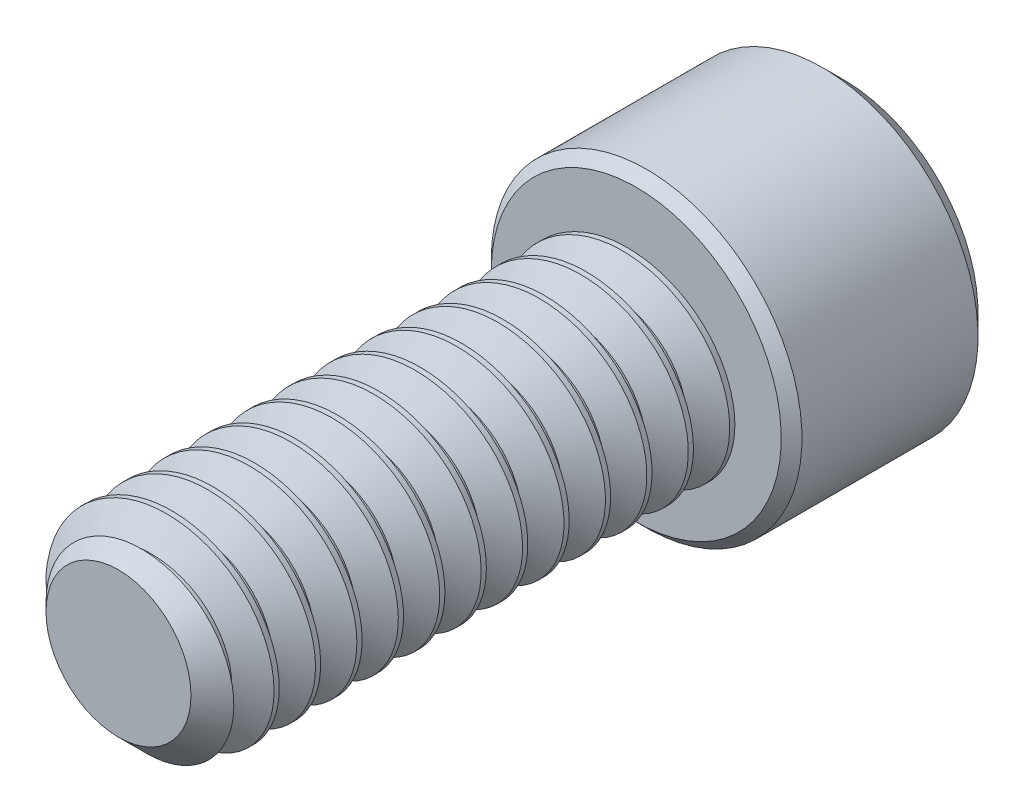
SolidWorks part; units mm, degrees
ref_plane "Front Plane" through (0, 0, 0) normal (0, 0, 1) x (1, 0, 0)
ref_plane "Top Plane" through (0, 0, 0) normal (0, 1, 0) x (1, 0, 0)
ref_plane "Right Plane" through (0, 0, 0) normal (1, 0, 0) x (0, 0, -1)
sketch "Sketch1" plane through (0, 0, 0) normal (0, 0, 1) x (1, 0, 0)
  line L0 (0, 3.175) -> (0, -3.175) construction
  circle A0 centre (0, 0) radius 3.175
  dimension "OD" = 6.35
extrude "Extrude1" add sketch "Sketch1" against normal blind 15.875
sketch "Sketch2" plane through (0, 0, 0) normal (0, 0, 1) x (1, 0, 0)
  circle A0 centre (0, 0) radius 3.175 construction
  circle A1 centre (0, 0) radius 3.175
curve "Helix/Spiral1" pitch 1.27 height 17.145 turns 13.5 parameters "pitch"=1.27
chamfer "Chamfer3" distance 0.9525 angle 45 1 edges at (3.175, 0, 0)
sketch "Sketch3" plane through (0, 0, 0) normal (1, 0, 0) x (0, 0, -1)
  line L0 (-1.1113, 3.175) -> (-0.635, 2.3501)
  line L1 (-0.635, 2.3501) -> (-0.4763, 2.3501)
  line L2 (-0.4763, 2.3501) -> (0, 3.175)
  line L3 (-1.1113, 3.175) -> (0, 3.175)
  line L4 (-0.5556, 3.175) -> (-0.5556, 2.3501) construction
  line L5 (-0.8731, 2.7626) -> (-0.2381, 2.7626) construction
  line L6 (0, 3.175) -> (0, -3.175) construction
  dimension "D1" = 0.1588
  dimension "D2" = 0.635
  dimension "D3" = 60
sweep "Cut-Sweep1" cut profiles "Sketch3" path "Helix/Spiral1"
sketch "Sketch6" plane through (0, 0, -15.875) normal (0, 0, -1) x (-1, 0, 0)
  circle A0 centre (0, 0) radius 4.7625
  dimension "head dia" = 9.525
extrude "Extrude2" add sketch "Sketch6" along normal blind 6.35
sketch "Sketch7" plane through (0, 0, -22.225) normal (0, 0, -1) x (-1, 0, 0)
  line L1 (0, 2.7496) -> (-2.3813, 1.3748)
  line L2 (-2.3813, 1.3748) -> (-2.3813, -1.3748)
  line L3 (-2.3813, -1.3748) -> (0, -2.7496)
  line L4 (0, -2.7496) -> (2.3813, -1.3748)
  line L5 (2.3813, -1.3748) -> (2.3813, 1.3748)
  line L6 (2.3813, 1.3748) -> (0, 2.7496)
  circle A0 centre (0, 0) radius 2.3813 construction
  dimension "hex dia" = 4.7625
extrude "Cut-Extrude1" cut sketch "Sketch7" against normal blind 3.5719
sketch "Sketch8" plane through (0, 0, -22.225) normal (0, 0, -1) x (-1, 0, 0)
  circle A0 centre (0, 0) radius 2.7496
extrude "Cut-Extrude2" cut sketch "Sketch8" against normal blind 0.635 draft 45
chamfer "Chamfer1" distance 0.635 angle 45 1 edges at (-4.7625, 0, -22.225)
chamfer "Chamfer2" distance 0.3175 angle 45 1 edges at (-4.7625, 0, -15.875)
sketch "Sketch9" plane through (0, 0, 0) normal (1, 0, 0) x (0, 0, -1)
  line L0 (0, 3.175) -> (0, -3.175) construction
  line L1 (6.985, 3.175) -> (6.985, -3.175) construction
  line L2 (15.875, 4.7625) -> (15.875, -4.7625) construction
  line L3 (22.225, 4.7625) -> (22.225, -4.7625) construction
  line L4 (22.225, 0) -> (0, 0) construction
  dimension "D1" = 6.985
  dimension "D2" = 6.35
  dimension "D3" = 9.525
  dimension "D4" = 0.635
  dimension "D5" = 0.3302
equation "\"D3@Helix/Spiral1\" = \"screw length@Extrude1\"+\"pitch@Helix/Spiral1\""
equation "\"D1@Sketch3\" = \"pitch@Helix/Spiral1\"*.125"
equation "\"D2@Sketch3\" = \"pitch@Helix/Spiral1\"*.5"
equation "\"D1@Cut-Extrude1\" = \"hex dia@Sketch7\"*.75"
equation "\"D1@Chamfer1\" = \"head depth@Extrude2\"/10"
equation "\"D1@Sketch9\" = \"pitch@Helix/Spiral1\"*5.5"
equation "\"D1@Chamfer2\" = \"D1@Chamfer1\"/2"
equation "\"D1@Cut-Extrude2\" = \"D1@Chamfer2\"*2"
equation "\"D1@Chamfer3\" = \"pitch@Helix/Spiral1\"*.750"
equation "\"D2@Sketch9\" = \"head depth@Extrude2\""
equation "\"D3@Sketch9\" = \"head dia@Sketch6\""
equation "\"D4@Sketch9\" = \"screw length@Extrude1\""
